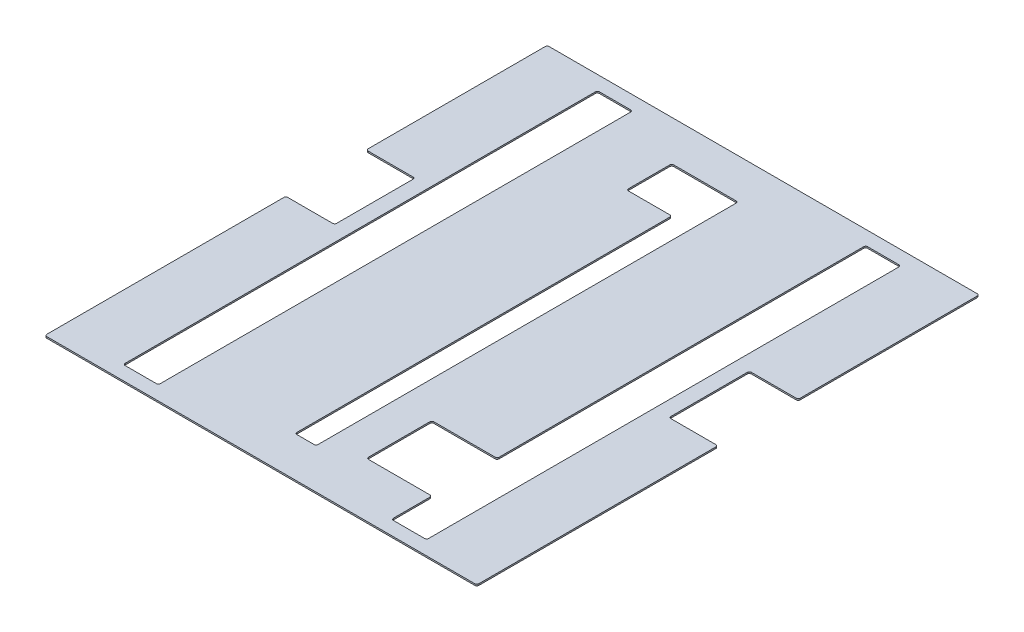
SolidWorks part; units mm, degrees
ref_plane "Front Plane" through (0, 0, 0) normal (0, 0, 1) x (1, 0, 0)
ref_plane "Top Plane" through (0, 0, 0) normal (0, 1, 0) x (1, 0, 0)
ref_plane "Right Plane" through (0, 0, 0) normal (1, 0, 0) x (0, 0, -1)
sketch "Sketch1" plane through (0, 0, 0) normal (0, 1, 0) x (1, 0, 0)
  line L1 (5911.0841, -8452.3124) -> (6341.0841, -8452.3124)
  line L2 (5911.0841, -8452.3124) -> (5911.0841, -8952.3124)
  line L3 (5911.0841, -8952.3124) -> (6341.0841, -8952.3124)
  line L4 (6341.0841, -8452.3124) -> (6341.0841, -8952.3124)
  dimension "D1" = 500
  dimension "D2" = 430
extrude "Boss-Extrude1" add sketch "Sketch1" along normal blind 1.5
sketch "Sketch2" plane through (0, 1.5, 0) normal (0, 1, 0) x (1, 0, 0)
  line L0 (5911.0841, -8452.3124) -> (5911.0841, -8952.3124) construction
  line L1 (5959.6841, -8712.448) -> (5911.0841, -8712.448)
  line L2 (5959.6841, -8712.448) -> (5959.6841, -8632.448)
  line L3 (5959.6841, -8632.448) -> (5911.0841, -8632.448)
  line L4 (5911.0841, -8712.448) -> (5911.0841, -8632.448)
  line L9 (6341.0841, -8952.3124) -> (6341.0841, -8452.3124) construction
  line L10 (6341.0841, -8712.448) -> (6292.4841, -8712.448)
  line L11 (6341.0841, -8712.448) -> (6341.0841, -8632.448)
  line L12 (6341.0841, -8632.448) -> (6292.4841, -8632.448)
  line L13 (6292.4841, -8712.448) -> (6292.4841, -8632.448)
  dimension "D1" = 48.6
  dimension "D2" = 80
  dimension "D3" = 80
  dimension "D4" = 48.6
extrude "Cut-Extrude1" cut sketch "Sketch2" against normal blind 10
sketch "Sketch3" plane through (0, 1.5, 0) normal (0, 1, 0) x (1, 0, 0)
  line L0 (5975.0841, -8541.6519) -> (5975.0841, -8938.3124)
  line L1 (6277.0841, -8938.3124) -> (6242.0841, -8938.3124)
  line L2 (6277.0841, -8938.3124) -> (6277.0841, -8466.3124)
  line L3 (6277.0841, -8466.3124) -> (6242.0841, -8466.3124)
  line L4 (6242.0841, -8938.3124) -> (6242.0841, -8466.3124)
  line L5 (5975.0841, -8466.3124) -> (6010.0841, -8466.3124)
  line L11 (5975.0841, -8938.3124) -> (6010.0841, -8938.3124)
  line L12 (6010.0841, -8466.3124) -> (6010.0841, -8938.3124)
  line L36 (5911.0841, -8712.448) -> (5911.0841, -8952.3124) construction
  line L37 (6341.0841, -8952.3124) -> (6341.0841, -8712.448) construction
  line L39 (6111.0841, -8492.3124) -> (6141.0841, -8492.3124)
  line L40 (6120.0841, -8537.3124) -> (6120.0841, -8912.3124)
  line L41 (6120.0841, -8912.3124) -> (6141.0841, -8912.3124)
  line L42 (6141.0841, -8492.3124) -> (6141.0841, -8912.3124)
  line L44 (6341.0841, -8452.3124) -> (5911.0841, -8452.3124) construction
  line L45 (5975.0841, -8466.3124) -> (5975.0841, -8541.6519)
  line L47 (5911.0841, -8952.3124) -> (6341.0841, -8952.3124) construction
  line L48 (6111.0841, -8492.3124) -> (6075.0841, -8492.3124)
  line L50 (6120.0841, -8537.3124) -> (6075.0841, -8537.3124)
  line L51 (6075.0841, -8492.3124) -> (6075.0841, -8537.3124)
  point P32 (6126.0841, -8452.3124)
  point P33 (6126.0841, -8492.3124)
  dimension "D15" = 40
  dimension "D22" = 45
  dimension "D1" = 35
  dimension "D2" = 472
  dimension "D3" = 35
  dimension "D4" = 472
  dimension "D6" = 64
  dimension "D7" = 45
  dimension "D8" = 64
  dimension "D10" = 420
  dimension "D11" = 110
  dimension "D20" = 14
  dimension "D21" = 14
extrude "Cut-Extrude2" cut sketch "Sketch3" against normal blind 10
sketch "Sketch4" plane through (0, 1.5, 0) normal (0, 1, 0) x (1, 0, 0)
  line L0 (6242.0841, -8466.3124) -> (6242.0841, -8938.3124) construction
  line L1 (6242.0841, -8898.0965) -> (6177.0841, -8898.0965)
  line L2 (6242.0841, -8898.0965) -> (6242.0841, -8833.0965)
  line L3 (6242.0841, -8833.0965) -> (6177.0841, -8833.0965)
  line L4 (6177.0841, -8898.0965) -> (6177.0841, -8833.0965)
  dimension "D1" = 65
  dimension "D2" = 65
extrude "Cut-Extrude3" cut sketch "Sketch4" against normal blind 10
fillet "Fillet2" radius 2 12 edges at (6292.4841, 0.75, 8632.448) (6341.0841, 0.75, 8632.448) (6341.0841, 0.75, 8712.448) (6292.4841, 0.75, 8712.448) (5959.6841, 0.75, 8632.448) (5959.6841, 0.75, 8712.448) (5911.0841, 0.75, 8712.448) (5911.0841, 0.75, 8632.448) (5911.0841, 0.75, 8452.3124) (6341.0841, 0.75, 8452.3124) (6341.0841, 0.75, 8952.3124) (5911.0841, 0.75, 8952.3124)
fillet "Fillet3" radius 2 18 edges at (6010.0841, 0.75, 8938.3124) (5975.0841, 0.75, 8938.3124) (6010.0841, 0.75, 8466.3124) (5975.0841, 0.75, 8466.3124) (6277.0841, 0.75, 8938.3124) (6242.0841, 0.75, 8938.3124) (6277.0841, 0.75, 8466.3124) (6242.0841, 0.75, 8466.3124) (6141.0841, 0.75, 8912.3124) (6120.0841, 0.75, 8912.3124) (6141.0841, 0.75, 8492.3124) (6120.0841, 0.75, 8537.3124) (6075.0841, 0.75, 8492.3124) (6075.0841, 0.75, 8537.3124) (6242.0841, 0.75, 8898.0965) (6242.0841, 0.75, 8833.0965) (6177.0841, 0.75, 8833.0965) (6177.0841, 0.75, 8898.0965)
